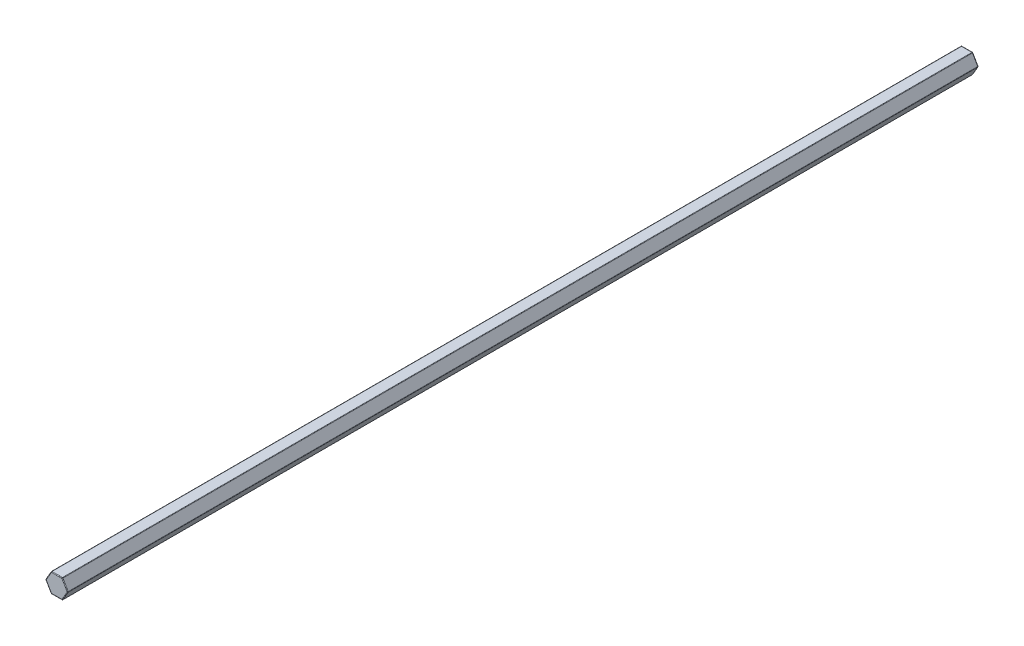
SolidWorks part; units mm, degrees
ref_plane "Front Plane" through (0, 0, 0) normal (0, 0, 1) x (1, 0, 0)
ref_plane "Top Plane" through (0, 0, 0) normal (0, 1, 0) x (1, 0, 0)
ref_plane "Right Plane" through (0, 0, 0) normal (1, 0, 0) x (0, 0, -1)
sketch "Sketch1" plane through (0, 0, 0) normal (0, 0, 1) x (1, 0, 0)
  line L1 (3.6662, 0) -> (1.8331, 3.175)
  line L2 (1.8331, 3.175) -> (-1.8331, 3.175)
  line L3 (-1.8331, 3.175) -> (-3.6662, 0)
  line L4 (-3.6662, 0) -> (-1.8331, -3.175)
  line L5 (-1.8331, -3.175) -> (1.8331, -3.175)
  line L6 (1.8331, -3.175) -> (3.6662, 0)
  circle A0 centre (0, 0) radius 3.175 construction
  point P1 (0, 0)
  dimension "D1" = 6.35
extrude "Boss-Extrude1" add sketch "Sketch1" along normal mid plane 300
fillet "Fillet1" radius 0.2 18 edges at (2.7496, 1.5875, -150) (-2.7496, 1.5875, -150) (0, -3.175, -150) (-3.6662, 0, 0) (-1.8331, -3.175, 0) (-2.7496, -1.5875, -150) (1.8331, -3.175, 0) (3.6662, 0, 0) (2.7496, -1.5875, -150) (1.8331, 3.175, 0) (-1.8331, 3.175, 0) (0, 3.175, -150) (0, -3.175, 150) (-2.7496, -1.5875, 150) (-2.7496, 1.5875, 150) (0, 3.175, 150) (2.7496, 1.5875, 150) (2.7496, -1.5875, 150)
ref_axis "Axis1" through (0, 0, -165) along (0, 0, 1)
